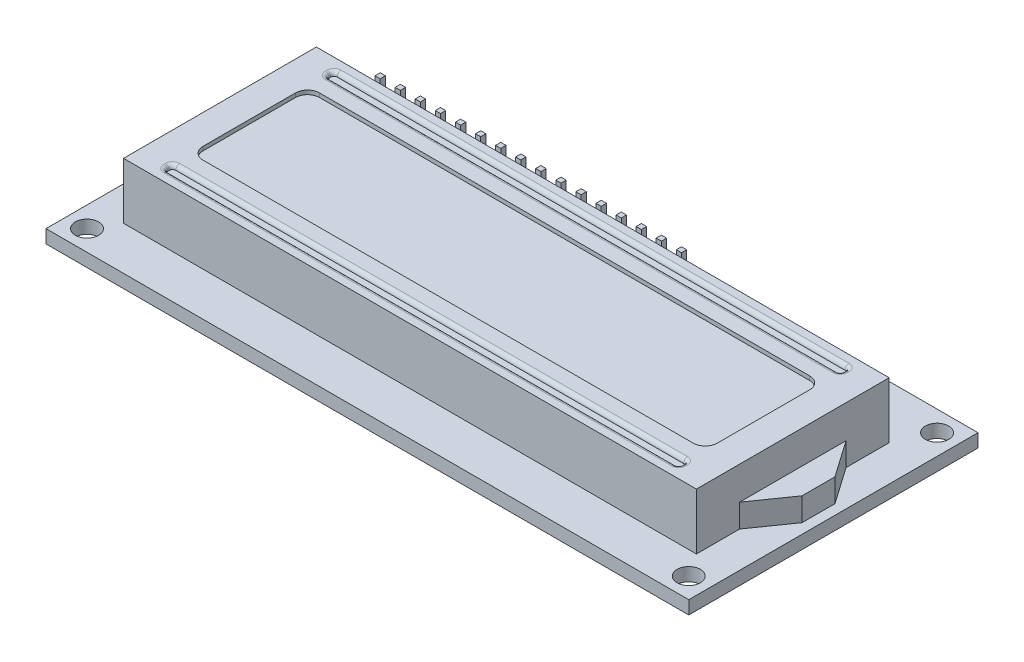
SolidWorks part; units mm, degrees
ref_plane "Front Plane" through (0, 0, 0) normal (0, 0, 1) x (1, 0, 0)
ref_plane "Top Plane" through (0, 0, 0) normal (0, 1, 0) x (1, 0, 0)
ref_plane "Right Plane" through (0, 0, 0) normal (1, 0, 0) x (0, 0, -1)
sketch "Sketch1" plane through (0, 0, 0) normal (0, 1, 0) x (1, 0, 0)
  line L1 (0, -18) -> (80, -18)
  line L2 (0, -18) -> (0, 18)
  line L3 (0, 18) -> (80, 18)
  line L4 (80, -18) -> (80, 18)
  dimension "D1" = 36
  dimension "D2" = 80
extrude "Boss-Extrude1" add sketch "Sketch1" along normal blind 1.65
sketch "Sketch2" plane through (0, 1.65, 0) normal (0, 1, 0) x (1, 0, 0)
  line L0 (0, 18) -> (0, -18) construction
  line L1 (4.25, -12.6) -> (75.55, -12.6)
  line L2 (4.25, -12.6) -> (4.25, 11.4)
  line L3 (4.25, 11.4) -> (75.55, 11.4)
  line L4 (75.55, -12.6) -> (75.55, 11.4)
  line L5 (80, -18) -> (80, 18) construction
  line L6 (0, -18) -> (80, -18) construction
  line L7 (80, 18) -> (0, 18) construction
  dimension "D1" = 71.3
  dimension "D2" = 24
  dimension "D3" = 4.25
  dimension "D4" = 4.45
  dimension "D5" = 5.4
  dimension "D6" = 6.6
extrude "Boss-Extrude2" add sketch "Sketch2" along normal blind 7
sketch "Sketch3" plane through (0, 1.65, 0) normal (0, 1, 0) x (1, 0, 0)
  line L0 (0, 18) -> (0, -18) construction
  line L1 (7.8, 15.8) -> (8.45, 15.8)
  line L2 (7.8, 15.8) -> (7.8, 15.15)
  line L3 (7.8, 15.15) -> (8.45, 15.15)
  line L4 (8.45, 15.8) -> (8.45, 15.15)
  line L5 (80, 18) -> (0, 18) construction
  dimension "D1" = 0.65
  dimension "D2" = 7.8
  dimension "D3" = 2.2
extrude "Boss-Extrude3" add sketch "Sketch3" along normal blind 3.8 and the other way blind 5
fillet "Fillet1" radius 0.5 4 edges at (8.125, 1.65, -15.15) (7.8, 1.65, -15.475) (8.45, 1.65, -15.475) (8.125, 1.65, -15.8)
pattern_linear "LPattern1" count 16 spacing 2.5 along (1, 0, 0) of "Boss-Extrude3", "Fillet1"
sketch "Sketch4" plane through (0, 8.65, 0) normal (0, 1, 0) x (1, 0, 0)
  line L0 (4.25, -0.6) -> (75.55, -0.6) construction
  line L1 (4.25, 11.4) -> (4.25, -12.6) construction
  line L2 (75.55, -12.6) -> (75.55, 11.4) construction
  line L3 (39.9, 11.4) -> (39.9, -12.6) construction
  line L4 (9.4, 6.65) -> (70.4, 6.65)
  line L5 (7.9, 5.15) -> (7.9, -6.35)
  line L6 (9.4, -7.85) -> (70.4, -7.85)
  line L7 (71.9, 5.15) -> (71.9, -6.35)
  line L8 (8.3, 9.95) -> (71.5, 9.95)
  line L9 (7.9, 9.55) -> (7.9, 9.35)
  line L10 (8.3, 8.95) -> (71.5, 8.95)
  line L11 (71.9, 9.55) -> (71.9, 9.35)
  line L12 (8.3, -10.15) -> (71.5, -10.15)
  line L13 (7.9, -10.55) -> (7.9, -10.75)
  line L14 (8.3, -11.15) -> (71.5, -11.15)
  line L15 (71.9, -10.55) -> (71.9, -10.75)
  line L16 (75.55, 11.4) -> (4.25, 11.4) construction
  line L17 (4.25, -12.6) -> (75.55, -12.6) construction
  arc A0 (70.4, -7.85) -> (71.9, -6.35) centre (70.4, -6.35) ccw
  arc A1 (70.4, 6.65) -> (71.9, 5.15) centre (70.4, 5.15) cw
  arc A2 (7.9, -6.35) -> (9.4, -7.85) centre (9.4, -6.35) ccw
  arc A3 (9.4, 6.65) -> (7.9, 5.15) centre (9.4, 5.15) ccw
  arc A4 (7.9, -10.75) -> (8.3, -11.15) centre (8.3, -10.75) ccw
  arc A5 (8.3, -10.15) -> (7.9, -10.55) centre (8.3, -10.55) ccw
  arc A6 (71.5, -11.15) -> (71.9, -10.75) centre (71.5, -10.75) ccw
  arc A7 (71.5, -10.15) -> (71.9, -10.55) centre (71.5, -10.55) cw
  arc A8 (71.5, 8.95) -> (71.9, 9.35) centre (71.5, 9.35) ccw
  arc A9 (71.5, 9.95) -> (71.9, 9.55) centre (71.5, 9.55) cw
  arc A10 (7.9, 9.35) -> (8.3, 8.95) centre (8.3, 9.35) ccw
  arc A11 (8.3, 9.95) -> (7.9, 9.55) centre (8.3, 9.55) ccw
  point P26 (71.9, -7.85)
  point P29 (71.9, 6.65)
  point P44 (71.9, 8.95)
  point P47 (71.9, 9.95)
  point P52 (7.9, 9.95)
  dimension "D5" = 1.5
  dimension "D6" = 0.4
  dimension "D1" = 64
  dimension "D2" = 14.5
  dimension "D3" = 1
  dimension "D4" = 2.3
extrude "Cut-Extrude1" cut sketch "Sketch4" against normal blind 0.5
fillet "Fillet3" radius 0.5 16 edges at (71.7828, 8.65, 10.2672) (71.9, 8.65, 10.65) (71.7828, 8.65, 11.0328) (39.9, 8.65, 11.15) (8.0172, 8.65, 11.0328) (7.9, 8.65, 10.65) (8.0172, 8.65, 10.2672) (71.7828, 8.65, -9.8328) (71.9, 8.65, -9.45) (71.7828, 8.65, -9.0672) (39.9, 8.65, -8.95) (8.0172, 8.65, -9.0672) (7.9, 8.65, -9.45) (8.0172, 8.65, -9.8328) (39.9, 8.65, 10.15) (39.9, 8.65, -9.95)
sketch "Sketch5" plane through (0, 1.65, 0) normal (0, 1, 0) x (1, 0, 0)
  line L0 (75.55, -0.6) -> (80, -0.6) construction
  line L1 (75.55, -12.6) -> (75.55, 11.4) construction
  line L2 (80, -18) -> (80, 18) construction
  line L3 (75.55, 6.025) -> (75.55, -7.225)
  line L4 (75.55, -12.6) -> (75.55, 11.4) construction
  line L5 (75.55, -7.225) -> (78.75, -2.65)
  line L6 (78.75, -2.65) -> (78.75, 1.45)
  line L7 (78.75, 1.45) -> (75.55, 6.025)
  dimension "D1" = 4.1
  dimension "D2" = 13.25
  dimension "D3" = 3.2
extrude "Boss-Extrude4" add sketch "Sketch5" along normal blind 2.9
sketch "Sketch6" plane through (0, 1.65, 0) normal (0, 1, 0) x (1, 0, 0)
  line L0 (40, 18) -> (40, -18) construction
  line L1 (80, 18) -> (0, 18) construction
  line L2 (0, -18) -> (80, -18) construction
  line L3 (0, 0) -> (80, 0) construction
  line L4 (80, -18) -> (80, 18) construction
  line L5 (0, 18) -> (0, -18) construction
  circle A0 centre (2.55, 15.45) radius 1.45
  circle A1 centre (77.45, 15.45) radius 1.45
  circle A2 centre (77.45, -15.45) radius 1.45
  circle A3 centre (2.55, -15.45) radius 1.45
  dimension "D1" = 2.9
  dimension "D2" = 1.1
  dimension "D3" = 1.1
extrude "Cut-Extrude2" cut sketch "Sketch6" against normal through all
ref_plane "Plane1" through (0, -4.95, 0) normal (0, -1, 0) x (-1, 0, 0)
sketch "Sketch9" plane through (0, 0, 0) normal (0, -1, 0) x (1, 0, 0)
  line L0 (73.2104, -9.4463) -> (72.75, -7.5)
  line L1 (73.2104, -9.4463) -> (66.6416, -11)
  line L2 (72.75, -7.5) -> (66.1812, -9.0537)
  line L3 (66.6416, -11) -> (66.1812, -9.0537)
  line L4 (73.2104, 10.5537) -> (72.75, 12.5)
  line L5 (73.2104, 10.5537) -> (66.6416, 9)
  line L6 (72.75, 12.5) -> (66.1812, 10.9463)
  line L7 (66.6416, 9) -> (66.1812, 10.9463)
  line L8 (44.2104, 10.5537) -> (43.75, 12.5)
  line L9 (44.2104, 10.5537) -> (37.6416, 9)
  line L10 (43.75, 12.5) -> (37.1812, 10.9463)
  line L11 (37.6416, 9) -> (37.1812, 10.9463)
  line L12 (15.2104, 10.5537) -> (14.75, 12.5)
  line L13 (15.2104, 10.5537) -> (8.6416, 9)
  line L14 (14.75, 12.5) -> (8.1812, 10.9463)
  line L15 (8.6416, 9) -> (8.1812, 10.9463)
  line L16 (72.75, 12.5) -> (14.75, 12.5) construction
  line L17 (72.75, 12.5) -> (72.75, -7.5) construction
  line L18 (0, 18) -> (80, 18) construction
  line L19 (80, 18) -> (80, -18) construction
  point P17 (43.75, 12.5)
  dimension "D1" = 2
  dimension "D2" = 6.75
  dimension "D3" = 2
  dimension "D4" = 6.75
  dimension "D5" = 2
  dimension "D6" = 6.75
  dimension "D7" = 2
  dimension "D8" = 6.75
  dimension "D9" = 29
  dimension "D10" = 20
  dimension "D11" = 5.5
  dimension "D12" = 7.25
  dimension "D13" = 3.5
  dimension "D14" = 3.5
  dimension "D15" = 3.5
  dimension "D16" = 3.5
extrude "Boss-Extrude7" add sketch "Sketch9" along normal blind 2.35
